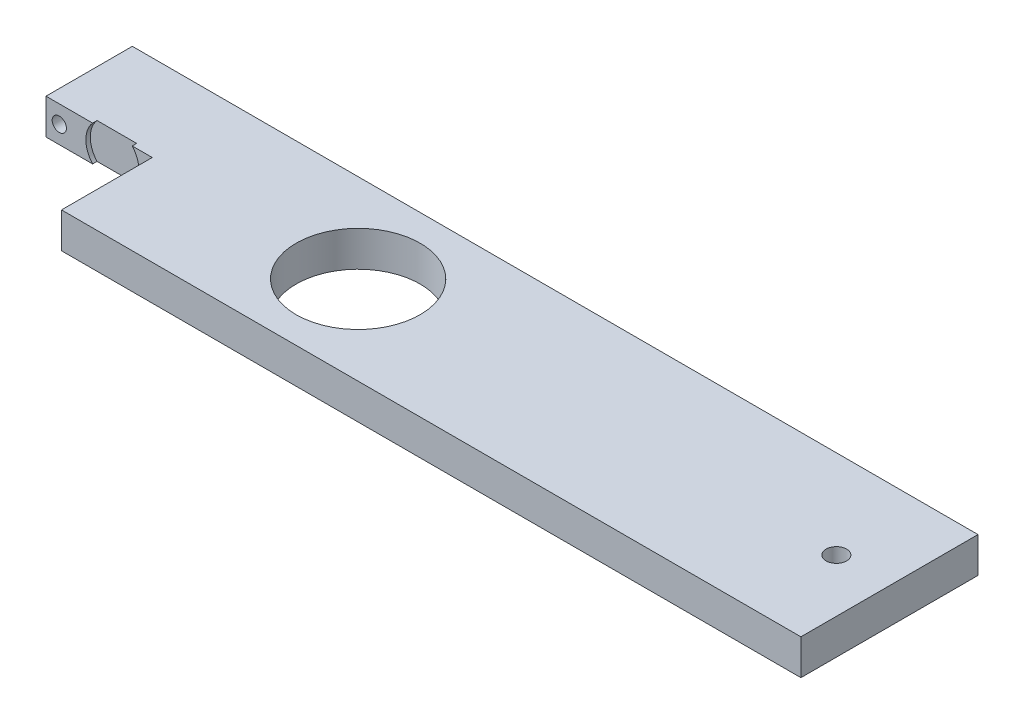
SolidWorks part; units mm, degrees
material "6061-T6 (SS)"
ref_plane "Front Plane" through (0, 0, 0) normal (0, 0, 1) x (1, 0, 0)
ref_plane "Top Plane" through (0, 0, 0) normal (0, 1, 0) x (1, 0, 0)
ref_plane "Right Plane" through (0, 0, 0) normal (1, 0, 0) x (0, 0, -1)
sketch "Sketch1" plane through (0, 0, 0) normal (0, 1, 0) x (1, 0, 0)
  line L0 (-114.3, 31.75) -> (-114.3, 0.7938) construction
  line L1 (-112.7125, 31.75) -> (190.5, 31.75)
  line L2 (-190.5, 31.75) -> (-190.5, -31.75) construction
  line L3 (-74.6125, -31.75) -> (190.5, -31.75)
  line L4 (190.5, 31.75) -> (190.5, -31.75)
  line L5 (-190.5, 31.75) -> (190.5, -31.75) construction
  line L6 (-190.5, -31.75) -> (190.5, 31.75) construction
  line L7 (-112.7125, 0.7938) -> (-76.2, 0.7938)
  line L8 (-76.2, 0.7938) -> (-76.2, -31.75) construction
  line L9 (-190.5, 31.75) -> (-114.3, 31.75) construction
  line L10 (-190.5, -31.75) -> (-76.2, -31.75) construction
  line L11 (-112.7125, 31.75) -> (-112.7125, 0.7938)
  line L12 (-74.6125, -31.75) -> (-74.6125, 0.7938)
  line L13 (-74.6125, 0.7938) -> (-76.2, 0.7938)
  line L14 (-114.3, 0.7938) -> (-112.7125, 0.7938) construction
  line L15 (-114.3, 31.75) -> (-112.7125, 31.75) construction
  line L16 (-76.2, -31.75) -> (-74.6125, -31.75) construction
  point P0 (0, 0)
  dimension "D1" = 381
  dimension "D2" = 63.5
  dimension "D3" = 0.7937
  dimension "D4" = 38.1
  dimension "D5" = 76.2
  dimension "D6" = 1.5875
  dimension "D7" = 1.5875
extrude "Boss-Extrude1" add sketch "Sketch1" along normal blind 12.7
sketch "Sketch2" plane through (0, 12.7, 0) normal (0, 1, 0) x (1, 0, 0)
  circle A0 centre (0, 0) radius 22.225
  dimension "D1" = 44.45
extrude "Cut-Extrude1" cut sketch "Sketch2" against normal through all
sketch "Sketch4" plane through (0, 12.7, 0) normal (0, 1, 0) x (1, 0, 0)
  line L2 (171.45, 0) -> (190.5, 0) construction
  line L3 (190.5, -31.75) -> (190.5, 31.75) construction
  circle A1 centre (171.45, 0) radius 3.683
  point P0 (171.45, -7.6743)
  dimension "D1" = 7.366
  dimension "D2" = 19.05
extrude "Cut-Extrude3" cut sketch "Sketch4" against normal through all
hole_wizard "#10 Clearance Hole1" positions "Sketch5" profile "Sketch6" hole size "#10" standard "ANSI Inch" end condition through all
sketch "Sketch5" plane through (0, 0, -31.75) normal (0, 0, -1) x (-1, 0, 0)
  line L1 (114.3, 0) -> (107.95, 6.35) construction
  line L2 (107.95, 6.35) -> (114.3, 12.7) construction
  line L3 (114.3, -987.3) -> (114.3, 49012.7) construction
  line L4 (112.7125, 12.7) -> (112.7125, 0) construction
  line L5 (-190.5, 12.7) -> (112.7125, 12.7) construction
  line L6 (-190.5, 0) -> (112.7125, 0) construction
  point P0 (107.95, 6.35)
  dimension "D1" = 6.35
  dimension "D2" = 1.5875
sketch "Sketch6" plane through (-107.95, 6.35, -31.75) normal (1, 0, 0) x (0, 1, 0)
  line L0 (0, 0) -> (0, 63.5)
  line L1 (0, 63.5) -> (2.5527, 63.5)
  line L2 (2.5527, 63.5) -> (2.5527, 0)
  line L5 (2.5527, 0) -> (0, 0)
  line L11 (0, -6.35) -> (0, 107.95) construction
  dimension "Thru Hole Dia." = 5.1054
  dimension "Thru Hole Depth" = 63.5
sketch "Sketch7" plane through (0, 0, -0.7938) normal (0, 0, 1) x (1, 0, 0)
  line L0 (-88.9, 12.7) -> (-88.9, 6.35) construction
  line L1 (-112.7125, 12.7) -> (-74.6125, 12.7) construction
  line L2 (-88.9, 6.35) -> (-88.9, 0) construction
  line L3 (-112.7125, 0) -> (-74.6125, 0) construction
  line L5 (-76.2, -995.5919) -> (-76.2, 49004.4081) construction
  line L6 (-74.6125, 12.7) -> (-74.6125, 0) construction
  circle A0 centre (-88.9, 6.35) radius 9.525
  dimension "D1" = 19.05
  dimension "D2" = 12.7
  dimension "D3" = 1.5875
extrude "Cut-Extrude4" cut sketch "Sketch7" against normal blind 1.5875
